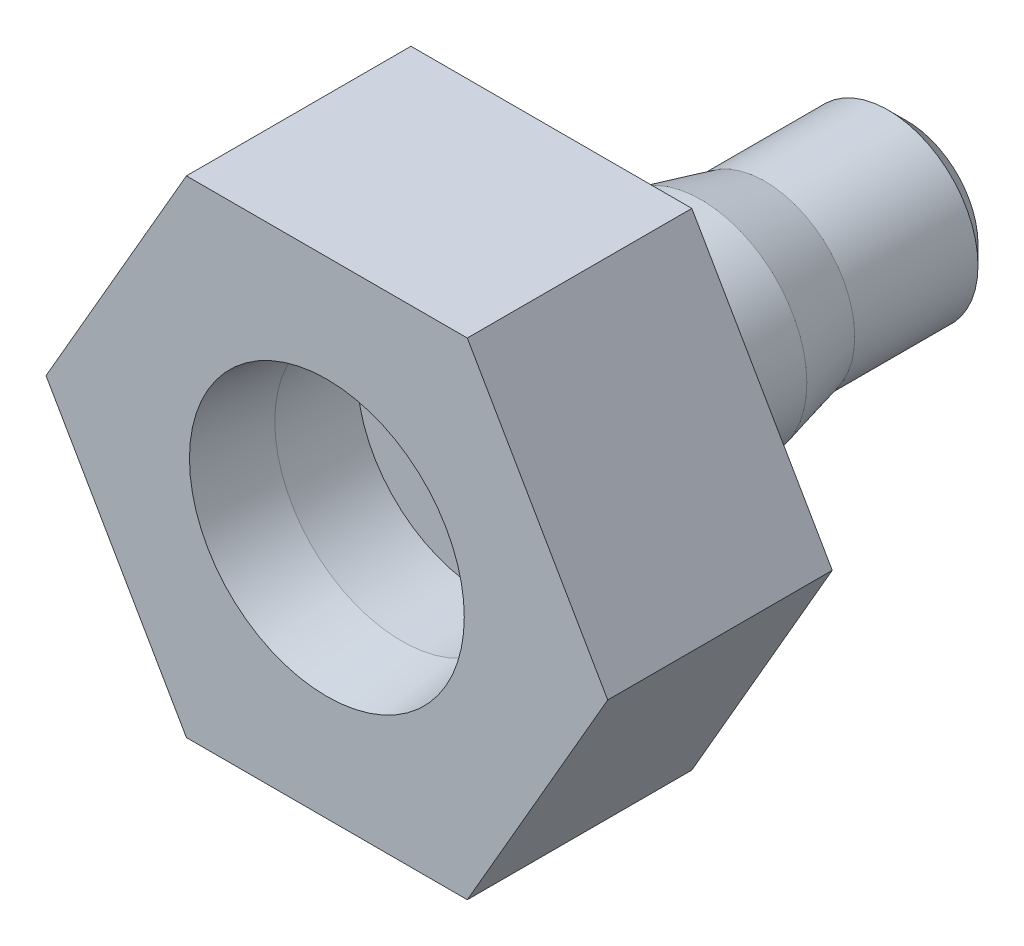
SolidWorks part; units mm, degrees
ref_plane "Front Plane" through (0, 0, 0) normal (0, 0, 1) x (1, 0, 0)
ref_plane "Top Plane" through (0, 0, 0) normal (0, 1, 0) x (1, 0, 0)
ref_plane "Right Plane" through (0, 0, 0) normal (1, 0, 0) x (0, 0, -1)
sketch "Sketch1" plane through (0, 0, 0) normal (0, 0, 1) x (1, 0, 0)
  circle A0 centre (0, 0) radius 2.825
  dimension "D1" = 5.65
extrude "Boss-Extrude1" add sketch "Sketch1" along normal blind 9.5
sketch "Sketch2" plane through (0, 0, 9.5) normal (0, 0, 1) x (1, 0, 0)
  circle A0 centre (0, 0) radius 6.5
  dimension "D1" = 13
extrude "Boss-Extrude2" add sketch "Sketch2" along normal blind 6 contours A0
sketch "Sketch3" plane through (0, 0, 15.5) normal (0, 0, 1) x (1, 0, 0)
  circle A0 centre (0, 0) radius 0.85
  dimension "D1" = 1.7
extrude "Cut-Extrude1" cut sketch "Sketch3" against normal up to surface (15.5 mm away) up to face at (2.825, 0, 0)
sketch "Sketch4" plane through (0, 0, 15.5) normal (0, 0, 1) x (1, 0, 0)
  circle A0 centre (0, 0) radius 2.5
  dimension "D1" = 5
extrude "Cut-Extrude2" cut sketch "Sketch4" against normal blind 4
chamfer "Chamfer1" distance 1 angle 45 1 edges at (2.825, 0, 9.5)
sketch "Sketch10" plane through (0, 0, 15.5) normal (0, 0, 1) x (1, 0, 0)
  line L1 (3.7528, 6.5) -> (-3.7528, 6.5)
  line L2 (-3.7528, 6.5) -> (-7.5056, 0)
  line L3 (-7.5056, 0) -> (-3.7528, -6.5)
  line L4 (-3.7528, -6.5) -> (3.7528, -6.5)
  line L5 (3.7528, -6.5) -> (7.5056, 0)
  line L6 (7.5056, 0) -> (3.7528, 6.5)
  circle A0 centre (0, 0) radius 11.55 construction
  circle A1 centre (0, 0) radius 0.85
  circle A2 centre (0, 0) radius 6.5 construction
  circle A3 centre (0, 0) radius 0.85 construction
extrude "Boss-Extrude5" add sketch "Sketch10" against normal up to surface (6 mm away) up to face at (3.825, 0, 9.5)
sketch "Sketch11" plane through (0, 0, 0) normal (0, 0, -1) x (-1, 0, 0)
  circle A0 centre (0, 0) radius 2.825
  circle A1 centre (0, 0) radius 2.825 construction
  circle A2 centre (0, 0) radius 2.4
  dimension "D1" = 4.8
extrude "Cut-Extrude3" cut sketch "Sketch11" against normal offset from surface (6 mm away) 3.5 up to face at (3.825, 0, 9.5)
chamfer "Chamfer2" distance 0.55 angle 76 1 edges at (2.4, 0, 6) first distance on face at (2.825, 0, 6)
chamfer "Chamfer3" distance 0.5 angle 45 1 edges at (-2.4, 0, 0)
sketch "Sketch12" plane through (0, 0, 15.5) normal (0, 0, 1) x (1, 0, 0)
  circle A0 centre (0, 0) radius 3.3909
  dimension "D1" = 6.7818
extrude "Cut-Extrude4" cut sketch "Sketch12" against normal blind 4.2
chamfer "Chamfer4" distance 2 angle 8 1 edges at (3.3909, 0, 15.5) first distance on face at (3.3909, 0, 11.3)
